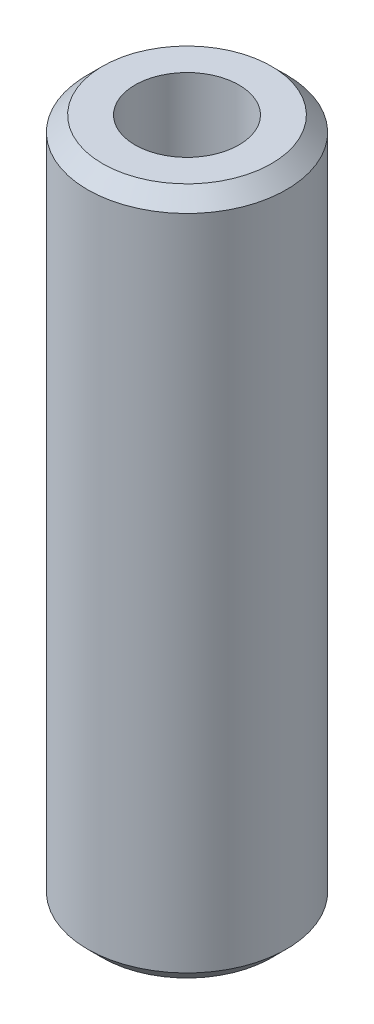
SolidWorks part; units mm, degrees
ref_plane "Front Plane" through (0, 0, 0) normal (0, 0, 1) x (1, 0, 0)
ref_plane "Top Plane" through (0, 0, 0) normal (0, 1, 0) x (1, 0, 0)
ref_plane "Right Plane" through (0, 0, 0) normal (1, 0, 0) x (0, 0, -1)
sketch "Sketch1" plane through (0, 0, 0) normal (0, 1, 0) x (1, 0, 0)
  circle A0 centre (0, 0) radius 32.5
  dimension "SHAFT_OD" = 65
extrude "Boss-Extrude1" add sketch "Sketch1" along normal blind 224.7347
sketch "Sketch2" plane through (0, 0, 0) normal (0, 1, 0) x (1, 0, 0)
  circle A0 centre (0, 0) radius 16.9886
  dimension "BORE_D" = 33.9773
extrude "Cut-Extrude1" cut sketch "Sketch2" along normal through all
chamfer "Chamfer1" distance 4.907 angle 45 2 edges at (0, 224.7347, 32.5) (0, 0, 32.5)
